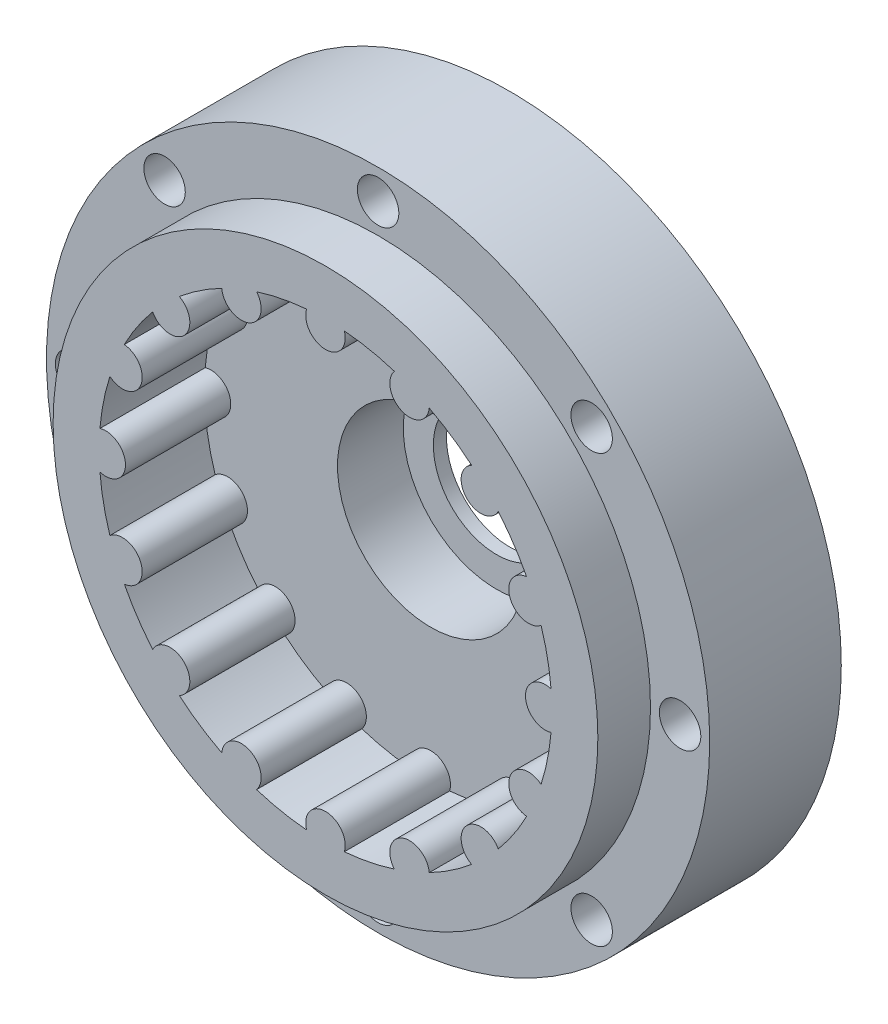
SolidWorks part; units mm, degrees
material "ABS"
ref_plane "Front Plane" through (0, 0, 0) normal (0, 0, 1) x (1, 0, 0)
ref_plane "Top Plane" through (0, 0, 0) normal (0, 1, 0) x (1, 0, 0)
ref_plane "Right Plane" through (0, 0, 0) normal (1, 0, 0) x (0, 0, -1)
sketch "Sketch1" plane through (0, 0, 0) normal (0, 0, 1) x (1, 0, 0)
  circle A0 centre (0, 0) radius 32.004
  dimension "D1" = 64.008
extrude "Boss-Extrude1" add sketch "Sketch1" along normal blind 12.7
sketch "Sketch2" plane through (0, 0, 12.7) normal (0, 0, 1) x (1, 0, 0)
  circle A0 centre (0, 0) radius 26.289
  circle A1 centre (0, 0) radius 32.004
  circle A2 centre (0, 0) radius 32.004
  dimension "D1" = 0
  dimension "D2" = 5.715
extrude "Cut-Extrude1" cut sketch "Sketch2" against normal blind 2.54 flip side to cut
sketch "Sketch3" plane through (0, 0, 10.16) normal (0, 0, 1) x (1, 0, 0)
  line L0 (0, 0) -> (0, 21.209) construction
  circle A1 centre (0, 21.209) radius 1.905
  circle A3 centre (0, 0) radius 21.209 construction
  circle A13 centre (8.1163, 19.5946) radius 1.905
  circle A14 centre (14.997, 14.997) radius 1.905
  circle A15 centre (19.5946, 8.1163) radius 1.905
  circle A16 centre (21.209, 0) radius 1.905
  circle A17 centre (19.5946, -8.1163) radius 1.905
  circle A18 centre (14.997, -14.997) radius 1.905
  circle A19 centre (8.1163, -19.5946) radius 1.905
  circle A20 centre (0, -21.209) radius 1.905
  circle A21 centre (-8.1163, -19.5946) radius 1.905
  circle A22 centre (-14.997, -14.997) radius 1.905
  circle A23 centre (-19.5946, -8.1163) radius 1.905
  circle A24 centre (-21.209, 0) radius 1.905
  circle A25 centre (-19.5946, 8.1163) radius 1.905
  circle A26 centre (-14.997, 14.997) radius 1.905
  circle A27 centre (-8.1163, 19.5946) radius 1.905
  dimension "D2" = 3.81
  dimension "D3" = 16
  dimension "D1" = 42.418
  dimension "D4" = 21.209
sketch "Sketch4" plane through (0, 0, 10.16) normal (0, 0, 1) x (1, 0, 0)
  circle A39 centre (0, 0) radius 27.559 construction
  circle A40 centre (0, 0) radius 13.589
  circle A41 centre (0, 0) radius 26.289 construction
  dimension "D2" = 55.118
  dimension "D1" = 13.97
extrude "Cut-Extrude3" cut sketch "Sketch4" against normal blind 2.54 contours A40 region at (0, 0, 10.16)
sketch "Sketch5" plane through (0, 0, 7.62) normal (0, 0, 1) x (1, 0, 0)
  circle A0 centre (0, 0) radius 9
  circle A1 centre (0, 0) radius 6.1
  dimension "D1" = 18
  dimension "D2" = 12.2
extrude "Cut-Extrude4" cut sketch "Sketch5" against normal through all contours A1 region at (0, 0, 7.62)
sketch "Sketch6" plane through (0, 0, 12.7) normal (0, 0, 1) x (1, 0, 0)
  line L0 (0, 0) -> (0, 32.004) construction
  line L1 (0, 0) -> (22.6302, 22.6302) construction
  line L2 (0, 0) -> (32.004, 0) construction
  line L3 (0, 0) -> (22.6302, -22.6302) construction
  line L4 (0, 0) -> (0, -32.004) construction
  line L5 (0, 0) -> (-22.6302, -22.6302) construction
  line L6 (0, 0) -> (-32.004, 0) construction
  line L7 (0, 0) -> (-22.6302, 22.6302) construction
  line L8 (0, 0) -> (0, 29.1465) construction
  circle A0 centre (0, 0) radius 32.004 construction
  circle A1 centre (0, 29.1465) radius 2
  circle A2 centre (20.6097, 20.6097) radius 2
  circle A3 centre (29.1465, 0) radius 2
  circle A4 centre (20.6097, -20.6097) radius 2
  circle A5 centre (0, -29.1465) radius 2
  circle A6 centre (-20.6097, -20.6097) radius 2
  circle A7 centre (-29.1465, 0) radius 2
  circle A8 centre (-20.6097, 20.6097) radius 2
  point P6 (0, 29.1465)
  point P16 (20.6097, 20.6097)
  point P18 (29.1465, 0)
  point P20 (20.6097, -20.6097)
  point P22 (0, -29.1465)
  point P24 (-20.6097, -20.6097)
  point P26 (-29.1465, 0)
  point P28 (-20.6097, 20.6097)
  point P52 (0, 0)
  dimension "D3" = 4
  dimension "D1" = 29.1465
  dimension "D2" = 8
  dimension "D4" = 8
extrude "Cut-Extrude5" cut sketch "Sketch5<3>" against normal blind 6.35
sketch "Sketch5<3>" plane through (0, 0, 7.62) normal (0, 0, 1) x (1, 0, 0) same geometry as "Sketch5"
sketch "Sketch8" plane through (0, 0, 10.16) normal (0, 0, 1) x (1, 0, 0)
  circle A0 centre (0, 0) radius 21.844
  circle A1 centre (0, 0) radius 26.289
  circle A5 centre (0, 0) radius 26.289
  dimension "D1" = 0
extrude "Boss-Extrude2" add sketch "Sketch8" along normal blind 7.62
extrude "Boss-Extrude3" add sketch "Sketch3" along normal blind 7.62
extrude "Cut-Extrude6" cut sketch "Sketch6" against normal through all
sketch "Sketch9" plane through (0, 0, 10.16) normal (0, 0, 1) x (1, 0, 0)
  arc A32 (-1.8212, 21.768) -> (-6.6477, 20.8079) centre (0, 0) ccw
  arc A33 (-10.0128, 19.414) -> (-6.6477, 20.8079) centre (-8.1163, 19.5946) ccw
  arc A34 (-10.0128, 19.414) -> (-14.1045, 16.68) centre (0, 0) ccw
  arc A35 (-16.68, 14.1045) -> (-14.1045, 16.68) centre (-14.997, 14.997) ccw
  arc A36 (-16.68, 14.1045) -> (-19.414, 10.0128) centre (0, 0) ccw
  arc A37 (-20.8079, 6.6477) -> (-19.414, 10.0128) centre (-19.5946, 8.1163) ccw
  arc A38 (-20.8079, 6.6477) -> (-21.768, 1.8212) centre (0, 0) ccw
  arc A39 (-21.768, -1.8212) -> (-21.768, 1.8212) centre (-21.209, 0) ccw
  arc A40 (-21.768, -1.8212) -> (-20.8079, -6.6477) centre (0, 0) ccw
  arc A41 (-19.414, -10.0128) -> (-20.8079, -6.6477) centre (-19.5946, -8.1163) ccw
  arc A42 (-19.414, -10.0128) -> (-16.68, -14.1045) centre (0, 0) ccw
  arc A43 (-14.1045, -16.68) -> (-16.68, -14.1045) centre (-14.997, -14.997) ccw
  arc A44 (-14.1045, -16.68) -> (-10.0128, -19.414) centre (0, 0) ccw
  arc A45 (-6.6477, -20.8079) -> (-10.0128, -19.414) centre (-8.1163, -19.5946) ccw
  arc A46 (-6.6477, -20.8079) -> (-1.8212, -21.768) centre (0, 0) ccw
  arc A47 (1.8212, -21.768) -> (-1.8212, -21.768) centre (0, -21.209) ccw
  arc A48 (1.8212, -21.768) -> (6.6477, -20.8079) centre (0, 0) ccw
  arc A49 (10.0128, -19.414) -> (6.6477, -20.8079) centre (8.1163, -19.5946) ccw
  arc A50 (10.0128, -19.414) -> (14.1045, -16.68) centre (0, 0) ccw
  arc A51 (16.68, -14.1045) -> (14.1045, -16.68) centre (14.997, -14.997) ccw
  arc A52 (16.68, -14.1045) -> (19.414, -10.0128) centre (0, 0) ccw
  arc A53 (20.8079, -6.6477) -> (19.414, -10.0128) centre (19.5946, -8.1163) ccw
  arc A54 (20.8079, -6.6477) -> (21.768, -1.8212) centre (0, 0) ccw
  arc A55 (21.768, 1.8212) -> (21.768, -1.8212) centre (21.209, 0) ccw
  arc A56 (21.768, 1.8212) -> (20.8079, 6.6477) centre (0, 0) ccw
  arc A57 (19.414, 10.0128) -> (20.8079, 6.6477) centre (19.5946, 8.1163) ccw
  arc A58 (19.414, 10.0128) -> (16.68, 14.1045) centre (0, 0) ccw
  arc A59 (14.1045, 16.68) -> (16.68, 14.1045) centre (14.997, 14.997) ccw
  arc A60 (14.1045, 16.68) -> (10.0128, 19.414) centre (0, 0) ccw
  arc A61 (6.6477, 20.8079) -> (10.0128, 19.414) centre (8.1163, 19.5946) ccw
  arc A62 (6.6477, 20.8079) -> (1.8212, 21.768) centre (0, 0) ccw
  arc A63 (-1.8212, 21.768) -> (1.8212, 21.768) centre (0, 21.209) ccw
  arc A64 (-1.8212, 21.768) -> (-6.6477, 20.8079) centre (0, 0) ccw
  arc A65 (-10.0128, 19.414) -> (-6.6477, 20.8079) centre (-8.1163, 19.5946) ccw
  arc A66 (-10.0128, 19.414) -> (-14.1045, 16.68) centre (0, 0) ccw
  arc A67 (-16.68, 14.1045) -> (-14.1045, 16.68) centre (-14.997, 14.997) ccw
  arc A68 (-16.68, 14.1045) -> (-19.414, 10.0128) centre (0, 0) ccw
  arc A69 (-20.8079, 6.6477) -> (-19.414, 10.0128) centre (-19.5946, 8.1163) ccw
  arc A70 (-20.8079, 6.6477) -> (-21.768, 1.8212) centre (0, 0) ccw
  arc A71 (-21.768, -1.8212) -> (-21.768, 1.8212) centre (-21.209, 0) ccw
  arc A72 (-21.768, -1.8212) -> (-20.8079, -6.6477) centre (0, 0) ccw
  arc A73 (-19.414, -10.0128) -> (-20.8079, -6.6477) centre (-19.5946, -8.1163) ccw
  arc A74 (-19.414, -10.0128) -> (-16.68, -14.1045) centre (0, 0) ccw
  arc A75 (-14.1045, -16.68) -> (-16.68, -14.1045) centre (-14.997, -14.997) ccw
  arc A76 (-14.1045, -16.68) -> (-10.0128, -19.414) centre (0, 0) ccw
  arc A77 (-6.6477, -20.8079) -> (-10.0128, -19.414) centre (-8.1163, -19.5946) ccw
  arc A78 (-6.6477, -20.8079) -> (-1.8212, -21.768) centre (0, 0) ccw
  arc A79 (1.8212, -21.768) -> (-1.8212, -21.768) centre (0, -21.209) ccw
  arc A80 (1.8212, -21.768) -> (6.6477, -20.8079) centre (0, 0) ccw
  arc A81 (10.0128, -19.414) -> (6.6477, -20.8079) centre (8.1163, -19.5946) ccw
  arc A82 (10.0128, -19.414) -> (14.1045, -16.68) centre (0, 0) ccw
  arc A83 (16.68, -14.1045) -> (14.1045, -16.68) centre (14.997, -14.997) ccw
  arc A84 (16.68, -14.1045) -> (19.414, -10.0128) centre (0, 0) ccw
  arc A85 (20.8079, -6.6477) -> (19.414, -10.0128) centre (19.5946, -8.1163) ccw
  arc A86 (20.8079, -6.6477) -> (21.768, -1.8212) centre (0, 0) ccw
  arc A87 (21.768, 1.8212) -> (21.768, -1.8212) centre (21.209, 0) ccw
  arc A88 (21.768, 1.8212) -> (20.8079, 6.6477) centre (0, 0) ccw
  arc A89 (19.414, 10.0128) -> (20.8079, 6.6477) centre (19.5946, 8.1163) ccw
  arc A90 (19.414, 10.0128) -> (16.68, 14.1045) centre (0, 0) ccw
  arc A91 (14.1045, 16.68) -> (16.68, 14.1045) centre (14.997, 14.997) ccw
  arc A92 (14.1045, 16.68) -> (10.0128, 19.414) centre (0, 0) ccw
  arc A93 (6.6477, 20.8079) -> (10.0128, 19.414) centre (8.1163, 19.5946) ccw
  arc A94 (6.6477, 20.8079) -> (1.8212, 21.768) centre (0, 0) ccw
  arc A95 (-1.8212, 21.768) -> (1.8212, 21.768) centre (0, 21.209) ccw
  dimension "D1" = 0
extrude "Cut-Extrude7" cut sketch "Sketch9" against normal blind 2.54
